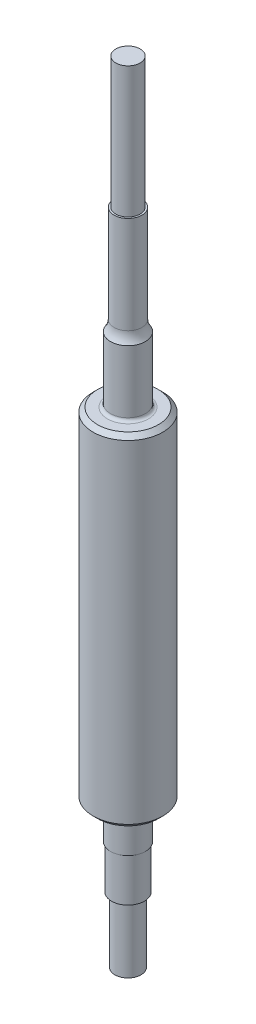
SolidWorks part; units mm, degrees
ref_plane "Front Plane" through (0, 0, 0) normal (0, 0, 1) x (1, 0, 0)
ref_plane "Top Plane" through (0, 0, 0) normal (0, 1, 0) x (1, 0, 0)
ref_plane "Right Plane" through (0, 0, 0) normal (1, 0, 0) x (0, 0, -1)
sketch "Sketch1" plane through (0, 0, 0) normal (0, 1, 0) x (1, 0, 0)
  circle A0 centre (0, 0) radius 7.975
  dimension "D1" = 15.95
extrude "Boss-Extrude1" add sketch "Sketch1" along normal blind 78.2
sketch "Sketch2" plane through (0, 78.2, 0) normal (0, 1, 0) x (1, 0, 0)
  circle A0 centre (0, 0) radius 4
  dimension "D1" = 8
extrude "Boss-Extrude2" add sketch "Sketch2" along normal blind 15
sketch "Sketch3" plane through (0, 0, 0) normal (0, -1, 0) x (1, 0, 0)
  circle A0 centre (0, 0) radius 4
  dimension "D1" = 8
extrude "Boss-Extrude3" add sketch "Sketch3" along normal blind 8
sketch "Sketch4" plane through (0, 93.2, 0) normal (0, 1, 0) x (1, 0, 0)
  circle A0 centre (0, 0) radius 3.195
  dimension "D1" = 6.39
extrude "Boss-Extrude4" add sketch "Sketch4" along normal blind 24.7
sketch "Sketch5" plane through (0, 117.9, 0) normal (0, 1, 0) x (1, 0, 0)
  circle A0 centre (0, 0) radius 2.79
  dimension "D1" = 5.58
extrude "Boss-Extrude5" add sketch "Sketch5" along normal blind 30
sketch "Sketch11" plane through (0, -8, 0) normal (0, -1, 0) x (1, 0, 0)
  circle A0 centre (0, 0) radius 3.76
  dimension "D1" = 7.52
extrude "Boss-Extrude7" add sketch "Sketch3<2>" along normal blind 8
sketch "Sketch3<2>" plane through (0, 0, 0) normal (0, -1, 0) x (1, 0, 0) same geometry as "Sketch3"
extrude "Boss-Extrude8" add sketch "Sketch11" along normal blind 10
sketch "Sketch12" plane through (0, -18, 0) normal (0, -1, 0) x (1, 0, 0)
  circle A0 centre (0, 0) radius 3
  dimension "D1" = 6
extrude "Boss-Extrude9" add sketch "Sketch12" along normal blind 15
chamfer "Chamfer6" distance 1 angle 45 1 edges at (0, 78.2, 7.975)
chamfer "Chamfer7" distance 1 angle 45 1 edges at (0, 0, 7.975)
fillet "Fillet1" radius 0.7 1 edges at (0, 78.2, 4)
fillet "Fillet3" radius 0.7 1 edges at (0, 0, -4)
fillet "Fillet4" radius 4 1 edges at (0, 93.2, 3.195)
